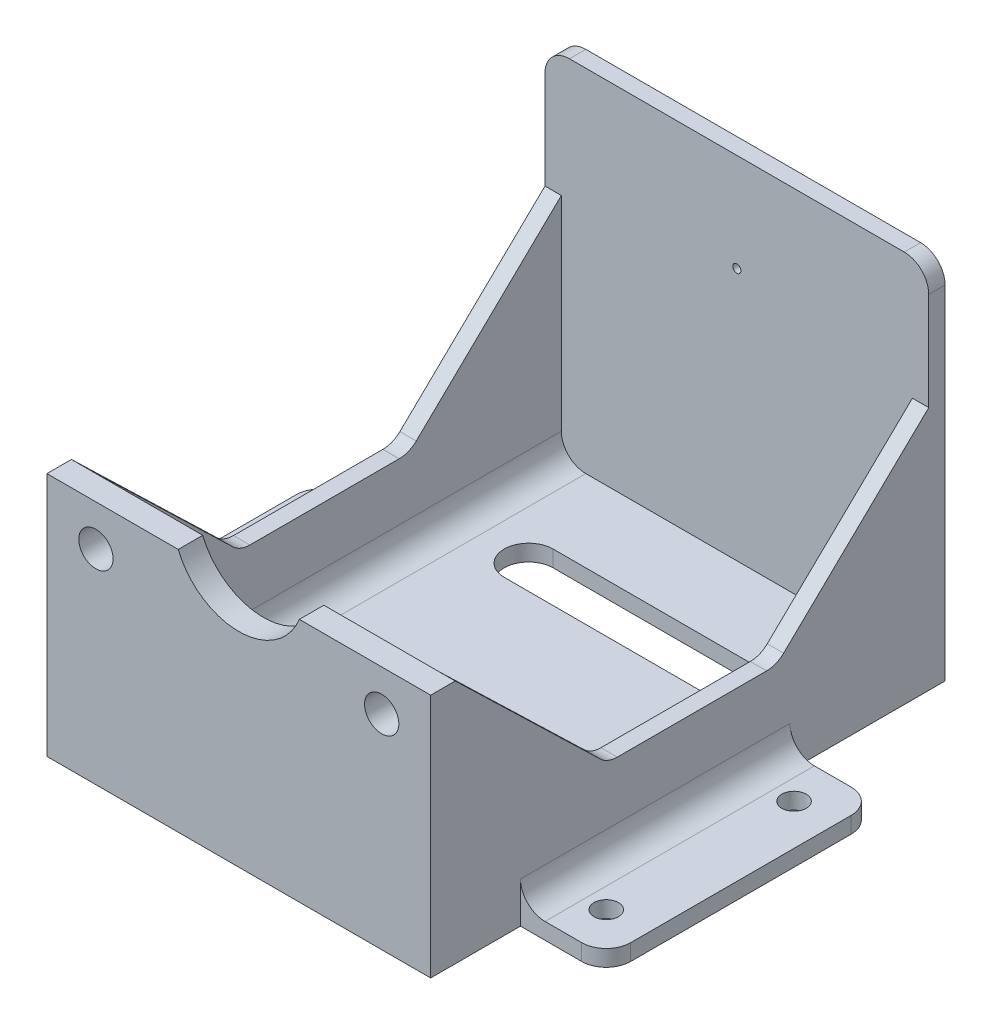
SolidWorks part; units mm, degrees
ref_plane "Front Plane" through (0, 0, 0) normal (0, 0, 1) x (1, 0, 0)
ref_plane "Top Plane" through (0, 0, 0) normal (0, 1, 0) x (1, 0, 0)
ref_plane "Right Plane" through (0, 0, 0) normal (1, 0, 0) x (0, 0, -1)
sketch "Sketch1" plane through (0, 0, 0) normal (0, 0, 1) x (1, 0, 0)
  line L0 (-17.5, 0) -> (0, 0) construction
  line L1 (0, 0) -> (0, 8) construction
  line L2 (7.4162, 5) -> (23.5, 5)
  line L3 (-23.5, -25) -> (23.5, -25)
  line L4 (-23.5, -25) -> (-23.5, 5)
  line L5 (-23.5, 5) -> (-7.4162, 5)
  line L6 (23.5, -25) -> (23.5, 5)
  line L7 (-23.5, -25) -> (23.5, 5) construction
  line L8 (-23.5, 5) -> (23.5, -25) construction
  line L9 (-7.4162, 5) -> (7.4162, 5) construction
  circle A0 centre (-17.5, 0) radius 2.1
  circle A1 centre (17.5, 0) radius 2.1
  arc A2 (-7.4162, 5) -> (7.4162, 5) centre (0, 8) ccw
  point P7 (0, -10)
  dimension "D1" = 4.2
  dimension "D3" = 6
  dimension "D4" = 5
  dimension "D5" = 8
  dimension "D2" = 35
  dimension "D6" = 8
  dimension "D7" = 30
extrude "Boss-Extrude1" add sketch "Sketch1" along normal blind 3
sketch "Sketch2" plane through (-23.5, 0, 0) normal (-1, 0, 0) x (0, 0, 1)
  line L0 (0, -25) -> (-60, -25)
  line L1 (-60, -25) -> (-60, 5)
  dimension "D1" = 60
  dimension "D2" = 30
extrude "Extrude-Thin1" add sketch "Sketch2" against normal up to surface (47 mm away) thin up to face at (23.5, -10, 1.5) thin type one direction wall 2
sketch "Sketch3" plane through (-23.5, 0, 0) normal (-1, 0, 0) x (0, 0, 1)
  line L0 (-58, 5) -> (-58, -23)
  line L1 (-58, -23) -> (0, -23)
  line L2 (0, -23) -> (0, 5)
  line L3 (0, 5) -> (-18.6429, -13)
  line L4 (-18.6429, -13) -> (-39.3571, -13)
  line L5 (-39.3571, -13) -> (-58, 5)
  line L6 (-39.3571, -13) -> (-29, -23) construction
  line L7 (-29, -23) -> (-18.6429, -13) construction
  line L8 (0, -23) -> (-58, -23) construction
  dimension "D1" = 10
extrude "Boss-Extrude2" add sketch "Sketch3" against normal blind 2 contours L5 L0 L1 L2 L3 L4
mirror "Mirror1" about plane through (0, 0, 0) normal (1, 0, 0) of "Boss-Extrude2"
sketch "Sketch4" plane through (0, -25, 0) normal (0, -1, 0) x (1, 0, 0)
  line L0 (-12.5, -5) -> (12.5, -5) construction
  line L1 (-12.5, -2) -> (12.5, -2)
  line L2 (-12.5, -8) -> (12.5, -8)
  line L3 (0, -5) -> (0, 0) construction
  line L4 (-12.5, -45) -> (12.5, -45) construction
  line L5 (-12.5, -42) -> (12.5, -42)
  line L6 (-12.5, -48) -> (12.5, -48)
  line L7 (-12.5, -5) -> (-12.5, -45) construction
  arc A0 (-12.5, -2) -> (-12.5, -8) centre (-12.5, -5) ccw
  arc A1 (12.5, -8) -> (12.5, -2) centre (12.5, -5) ccw
  arc A2 (-12.5, -42) -> (-12.5, -48) centre (-12.5, -45) ccw
  arc A3 (12.5, -48) -> (12.5, -42) centre (12.5, -45) ccw
  point P2 (0, -5)
  point P13 (0, -45)
  dimension "D1" = 3
  dimension "D2" = 5
  dimension "D3" = 25
  dimension "D4" = 2
  dimension "D5" = 40
extrude "Cut-Extrude1" cut sketch "Sketch4" against normal through all
sketch "Sketch6" plane through (0, 5, 0) normal (0, 1, 0) x (1, 0, 0)
  line L6 (21.5, 58) -> (23.5, 58)
  line L7 (23.5, 58) -> (23.5, 60)
  line L8 (23.5, 60) -> (-23.5, 60)
  line L9 (-23.5, 60) -> (-23.5, 58)
  line L10 (-23.5, 58) -> (-21.5, 58)
  line L11 (-21.5, 58) -> (21.5, 58)
  line L12 (21.5, 58) -> (23.5, 58)
  line L13 (23.5, 58) -> (23.5, 60)
  line L14 (23.5, 60) -> (-23.5, 60)
  line L15 (-23.5, 60) -> (-23.5, 58)
  line L16 (-23.5, 58) -> (-21.5, 58)
  line L17 (-21.5, 58) -> (21.5, 58)
  dimension "D1" = 0
extrude "Boss-Extrude3" add sketch "Sketch6" along normal blind 15
sketch "Sketch7" plane through (0, -25, 0) normal (0, -1, 0) x (1, 0, 0)
  line L0 (-12.5, -8) -> (12.5, -8) construction
  line L1 (-29, -36) -> (29, -36) construction
  line L2 (-29, -36) -> (-29, -13) construction
  line L3 (-29, -13) -> (29, -13) construction
  line L4 (29, -36) -> (29, -13) construction
  line L5 (-29, -36) -> (29, -13) construction
  line L6 (-29, -13) -> (29, -36) construction
  line L7 (-23.5, 3) -> (-23.5, -60) construction
  line L8 (0, -24.5) -> (0, 0) construction
  circle A0 centre (-29, -13) radius 1.5
  circle A1 centre (-29, -36) radius 1.5
  circle A2 centre (29, -36) radius 1.5
  circle A3 centre (29, -13) radius 1.5
  point P0 (0, -24.5)
  dimension "D3" = 3
  dimension "D1" = 58
  dimension "D2" = 23
  dimension "D4" = 5
  dimension "D5" = 5.5
sketch "Sketch9" plane through (0, -25, 0) normal (0, -1, 0) x (1, 0, 0)
  line L1 (-34, -8) -> (34, -8)
  line L2 (-34, -8) -> (-34, -41)
  line L3 (-34, -41) -> (34, -41)
  line L4 (34, -8) -> (34, -41)
  line L5 (29, -36) -> (29, -13) construction
  line L6 (0, -24.5) -> (34, -24.5) construction
  line L7 (-29, -13) -> (29, -13) construction
  line L8 (-29, -36) -> (-29, -13) construction
  dimension "D1" = 5
  dimension "D2" = 5
  dimension "D3" = 5
extrude "Boss-Extrude4" add sketch "Sketch9" against normal blind 2
extrude "Cut-Extrude2" cut sketch "Sketch7" against normal up to next
fillet "Fillet1" radius 3 2 edges at (21.5, -23, -29) (-21.5, -23, -29)
fillet "Fillet2" radius 3 12 edges at (-22.5, -13, -39.3571) (-22.5, -13, -18.6429) (22.5, -13, -18.6429) (22.5, -13, -39.3571) (-34, -24, -41) (-34, -24, -8) (34, -24, -41) (34, -24, -8) (23.5, -23, -24.5) (-23.5, -23, -24.5) (23.5, 20, -59) (-23.5, 20, -59)
sketch "Sketch10" plane through (0, 0, -58) normal (0, 0, 1) x (1, 0, 0)
  circle A0 centre (0, 8) radius 0.5
  dimension "D1" = 1
extrude "Cut-Extrude3" cut sketch "Sketch10" against normal up to next
